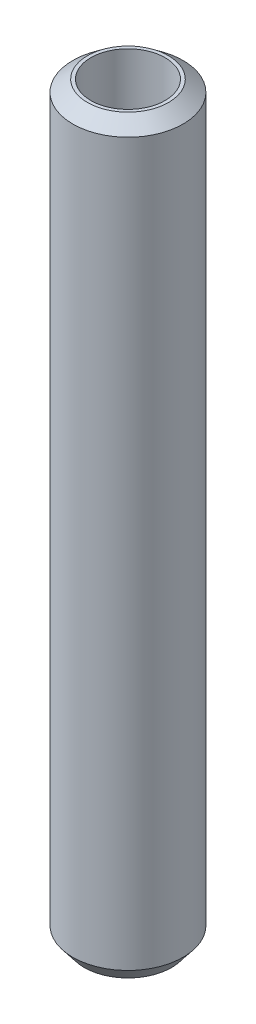
SolidWorks part; units mm, degrees
ref_plane "Front Plane" through (0, 0, 0) normal (0, 0, 1) x (1, 0, 0)
ref_plane "Top Plane" through (0, 0, 0) normal (0, 1, 0) x (1, 0, 0)
ref_plane "Right Plane" through (0, 0, 0) normal (1, 0, 0) x (0, 0, -1)
sketch "Sketch1" plane through (0, 0, 0) normal (0, 1, 0) x (1, 0, 0)
  circle A0 centre (0, 0) radius 27.5
  dimension "SHAFT_OD" = 55
extrude "Boss-Extrude1" add sketch "Sketch1" along normal blind 372.8879
sketch "Sketch2" plane through (0, 0, 0) normal (0, 1, 0) x (1, 0, 0)
  circle A0 centre (0, 0) radius 18.5376
  dimension "BORE_D" = 37.0751
extrude "Cut-Extrude1" cut sketch "Sketch2" along normal through all
chamfer "Chamfer1" distance 5.6852 angle 52.015 2 edges at (0, 372.8879, 27.5) (0, 0, 27.5) first distance on face at (0, 372.8879, 27.5) first distance on face at (0, 0, 18.5376)
